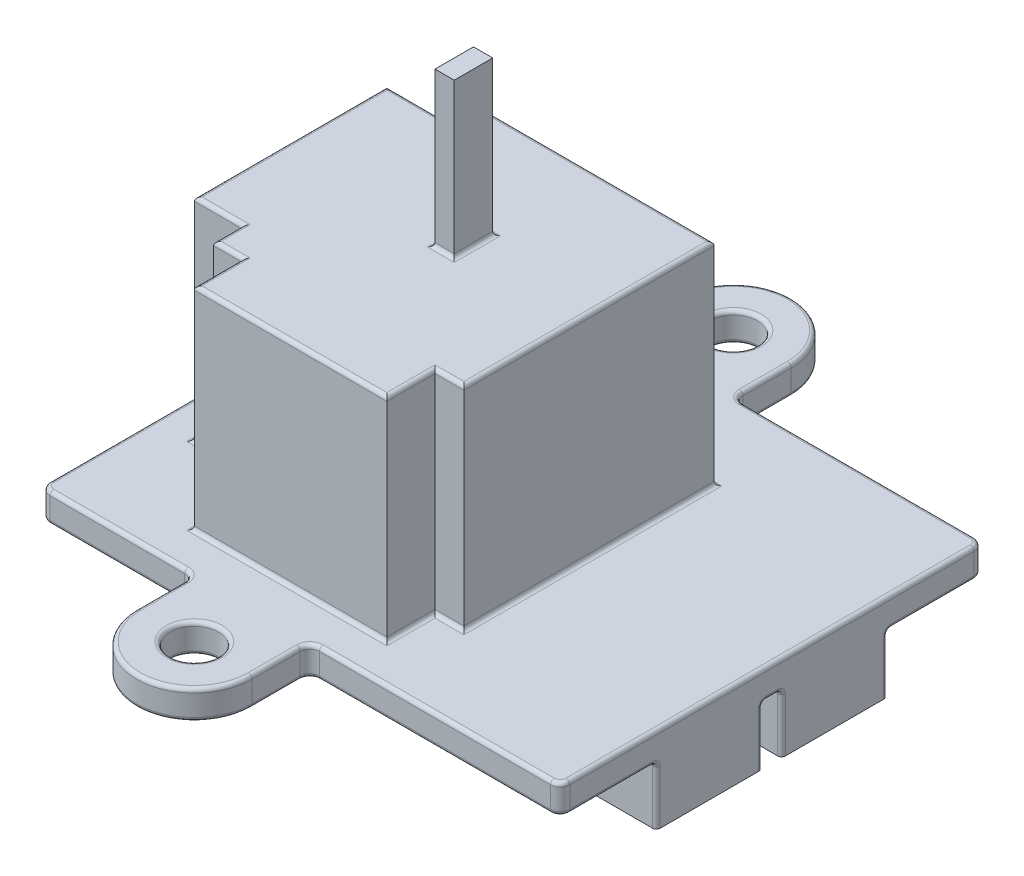
SolidWorks part; units mm, degrees
ref_plane "前视基准面" through (0, 0, 0) normal (0, 0, 1) x (1, 0, 0)
ref_plane "上视基准面" through (0, 0, 0) normal (0, 1, 0) x (1, 0, 0)
ref_plane "右视基准面" through (0, 0, 0) normal (1, 0, 0) x (0, 0, -1)
other "Configuration Table"
ref_axis "基准轴1" through (0, -46.8641, 0) along (0, 1, 0)
sketch "草图1" plane through (0, 0, 0) normal (0, 1, 0) x (1, 0, 0)
  line L2 (-3, -14) -> (-3, -11)
  line L3 (-11, 11) -> (16, 11)
  line L4 (-11, 11) -> (-11, -11)
  line L5 (-11, -11) -> (16, -11)
  line L6 (16, 11) -> (16, -11)
  line L7 (3, -14) -> (3, -11)
  line L8 (0, -14) -> (0, 14) construction
  line L9 (3, 14) -> (3, 11)
  line L10 (-3, 14) -> (-3, 11)
  circle A3 centre (0, -14) radius 1.25
  circle A4 centre (0, -14) radius 3
  circle A5 centre (0, 14) radius 1.25
  circle A6 centre (0, 14) radius 3
  point P12 (0, 0)
  dimension "D1" = 2.5
  dimension "D2" = 6
  dimension "D3" = 22
  dimension "D4" = 13
  dimension "D5" = 8
extrude "凸台-拉伸-PCB板" add sketch "草图1" along normal blind 1.5 contours L8 L5 L6 L3 | L5 L8 L3 L4 | A4 L5 L2 | A4 L7 L5 | A3 A4 | A6 L10 L3 | A6 L3 L9 | A6 A5 region at (-2.0613, 0, 11.9387) region at (-2.3299, 0, 11.6701) region at (-5.5, 0, 0) region at (2.3299, 0, 11.6701) region at (8, 0, 0) region at (2.3299, 0, -11.6701) region at (-2.3299, 0, -11.6701) region at (-2.0613, 0, -11.9387)
sketch "草图6" plane through (0, 0, 0) normal (0, -1, 0) x (1, 0, 0)
  line L0 (16, -11) -> (16, 11) construction
  line L1 (16, 6) -> (12, 6)
  line L2 (16, 6) -> (16, 0.5)
  line L3 (16, 0.5) -> (12, 0.5)
  line L4 (12, 6) -> (12, 0.5)
  line L5 (0, 0) -> (27.48, 0) construction
  line L6 (16, -0.5) -> (12, -0.5)
  line L7 (16, -0.5) -> (16, -6)
  line L8 (16, -6) -> (12, -6)
  line L9 (12, -0.5) -> (12, -6)
  dimension "D1" = 12
  dimension "D2" = 1
  dimension "D3" = 4
extrude "凸台-拉伸2" add sketch "草图6" along normal blind 3
sketch "草图3" plane through (0, 1.5, 0) normal (0, 1, 0) x (1, 0, 0)
  line L6 (-6.5, 6.5) -> (6.5, 6.5)
  line L7 (-6.5, 6.5) -> (-6.5, -6.5)
  line L8 (-6.5, -6.5) -> (6.5, -6.5)
  line L9 (6.5, 6.5) -> (6.5, -6.5)
  line L10 (-6.5, 6.5) -> (6.5, -6.5) construction
  line L11 (-6.5, -6.5) -> (6.5, 6.5) construction
  point P0 (0, 0)
  dimension "D1" = 13
extrude "凸台-拉伸-摇杆底座" add sketch "草图3" along normal blind 11
sketch "草图7" plane through (0, 0, 6.5) normal (0, 0, 1) x (1, 0, 0)
  line L0 (0, -46.8641) -> (0, 170.1769) construction
  line L1 (-5, 12.5) -> (5, 12.5)
  line L2 (-5, 12.5) -> (-5, 1.5)
  line L3 (-5, 1.5) -> (5, 1.5)
  line L4 (5, 12.5) -> (5, 1.5)
  line L5 (-5, 12.5) -> (5, 1.5) construction
  line L6 (-5, 1.5) -> (5, 12.5) construction
  line L7 (-6.5, 1.5) -> (6.5, 1.5) construction
  line L8 (-6.5, 12.5) -> (6.5, 12.5) construction
  point P0 (0, 7)
  dimension "D1" = 10
extrude "凸台-拉伸3" add sketch "草图7" along normal blind 2.5
sketch "草图8" plane through (-6.5, 0, 0) normal (-1, 0, 0) x (0, 0, 1)
  line L0 (0, -46.8641) -> (0, 170.1769) construction
  line L1 (-5, 12.5) -> (5, 12.5)
  line L2 (-5, 12.5) -> (-5, 1.5)
  line L3 (-5, 1.5) -> (5, 1.5)
  line L4 (5, 12.5) -> (5, 1.5)
  line L5 (-5, 12.5) -> (5, 1.5) construction
  line L6 (-5, 1.5) -> (5, 12.5) construction
  line L7 (-6.5, 1.5) -> (6.5, 1.5) construction
  line L8 (-6.5, 12.5) -> (6.5, 12.5) construction
  point P0 (0, 7)
  dimension "D1" = 10
extrude "凸台-拉伸4" add sketch "草图8" along normal blind 2.5
sketch "草图9" plane through (0, 12.5, 0) normal (0, 1, 0) x (1, 0, 0)
  line L1 (-0.5, 1) -> (0.5, 1)
  line L2 (-0.5, 1) -> (-0.5, -1)
  line L3 (-0.5, -1) -> (0.5, -1)
  line L4 (0.5, 1) -> (0.5, -1)
  line L5 (-0.5, 1) -> (0.5, -1) construction
  line L6 (-0.5, -1) -> (0.5, 1) construction
  point P0 (0, 0)
  dimension "D1" = 1
  dimension "D2" = 2
extrude "凸台-拉伸5" add sketch "草图9" along normal blind 8
fillet "圆角1" radius 0.5 8 edges at (-11, 0.75, -11) (-3, 0.75, 11) (-11, 0.75, 11) (3, 0.75, 11) (16, 0.75, -11) (16, 0.75, 11) (-3, 0.75, -11) (3, 0.75, -11)
fillet "圆角2" radius 0.2 84 edges at (16, -1.5, 6) (16, -1.5, 0.5) (16, -1.5, -0.5) (16, -1.5, -6) (5.75, 12.5, 6.5) (5, 12.5, 7.75) (0, 12.5, 9) (-5, 12.5, 7.75) (-5.75, 12.5, 6.5) (-6.5, 12.5, 5.75) (-7.75, 12.5, 5) (-9, 12.5, 0) (-7.75, 12.5, -5) (-6.5, 12.5, -5.75) (0, 12.5, -6.5) (6.5, 12.5, 0) (0, 12.5, -1) (-0.5, 12.5, 0) (0, 12.5, 1) (0.5, 12.5, 0) (-5.75, 1.5, 6.5) (-5, 1.5, 7.75) (0, 1.5, 9) (5, 1.5, 7.75) (5.75, 1.5, 6.5) (6.5, 1.5, 0) (0, 1.5, -6.5) (-6.5, 1.5, -5.75) (-7.75, 1.5, -5) (-9, 1.5, 0) (-7.75, 1.5, 5) (-6.5, 1.5, 5.75) (0, 1.5, 15.25) (0, 1.5, -12.75) (-3.1464, 1.5, -11.1464) (-3, 1.5, -12.75) (0, 1.5, -17) (3, 1.5, -12.75) (3.1464, 1.5, -11.1464) (9.5, 1.5, -11) (15.8536, 1.5, -10.8536) (16, 1.5, 0) (15.8536, 1.5, 10.8536) (9.5, 1.5, 11) (3.1464, 1.5, 11.1464) (3, 1.5, 12.75) (0, 1.5, 17) (-3, 1.5, 12.75) (-3.1464, 1.5, 11.1464) (-7, 1.5, 11) (-10.8536, 1.5, 10.8536) (-11, 1.5, 0) (-10.8536, 1.5, -10.8536) (-7, 1.5, -11) (-10.8536, 0, 10.8536) (-7, 0, 11) (-3.1464, 0, 11.1464) (-3, 0, 12.75) (0, 0, 17) (3, 0, 12.75) (3.1464, 0, 11.1464) (9.5, 0, 11) (15.8536, 0, 10.8536) (16, 0, 8.25) (14, 0, 6) (12, 0, 3.25) (14, 0, 0.5) (16, 0, 0) (14, 0, -0.5) (12, 0, -3.25) (14, 0, -6) (16, 0, -8.25) (15.8536, 0, -10.8536) (9.5, 0, -11) (3.1464, 0, -11.1464) (3, 0, -12.75) (0, 0, -17) (-3, 0, -12.75) (-3.1464, 0, -11.1464) (-7, 0, -11) (-10.8536, 0, -10.8536) (-11, 0, 0) (0, 0, 15.25) (0, 0, -12.75)
